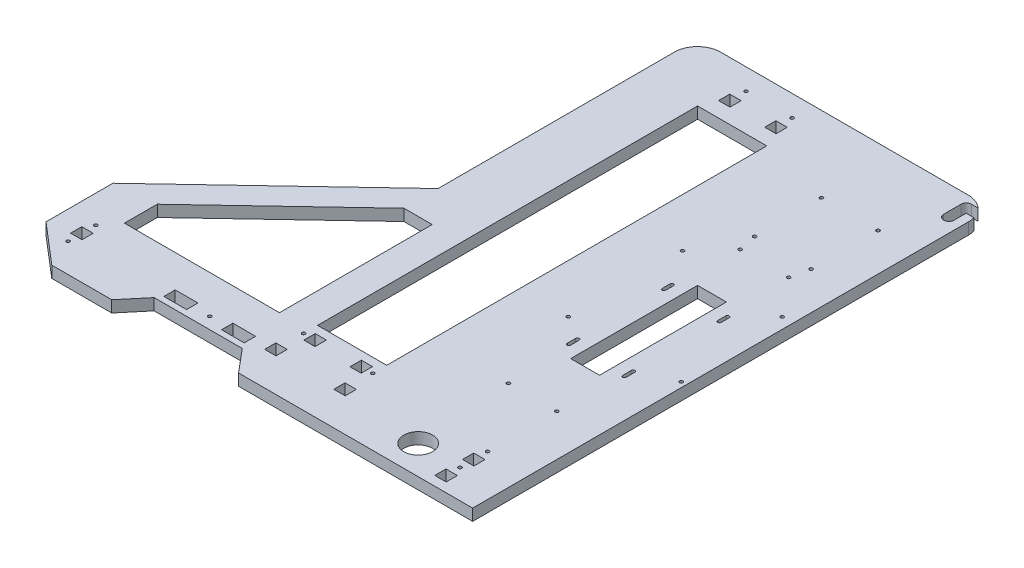
SolidWorks part; units mm, degrees
ref_plane "Front Plane" through (0, 0, 0) normal (0, 0, 1) x (1, 0, 0)
ref_plane "Top Plane" through (0, 0, 0) normal (0, 1, 0) x (1, 0, 0)
ref_plane "Right Plane" through (0, 0, 0) normal (1, 0, 0) x (0, 0, -1)
sketch "Sketch1" plane through (0, 0, 0) normal (0, 1, 0) x (1, 0, 0)
  line L0 (0, 0) -> (-235, 0)
  line L1 (-235, 0) -> (-235, -225)
  line L2 (-235, -225) -> (-380, -362)
  line L3 (-380, -362) -> (-380, -420)
  line L4 (-380, -420) -> (-345, -450)
  line L5 (-345, -450) -> (-293, -450)
  line L6 (-293, -450) -> (-263.6315, -415)
  line L7 (-263.6315, -415) -> (-212.3685, -415)
  line L8 (-212.3685, -415) -> (-183, -450)
  line L9 (-183, -450) -> (0, -450)
  line L10 (0, 0) -> (0, -450)
  line L12 (-293, -450) -> (-183, -450) construction
  dimension "D3" = 235
  dimension "D5" = 58
  dimension "D13" = 190
  dimension "D7" = 35
  dimension "D15" = 52
  dimension "D12" = 30
  dimension "D10" = 35
  dimension "D6" = 380
  dimension "D4" = 450
  dimension "D2" = 50
  dimension "D8" = 50
  dimension "D9" = 110
extrude "Boss-Extrude1" add sketch "Sketch1" along normal blind 10
sketch "Sketch16" plane through (0, 10, 0) normal (0, 1, 0) x (1, 0, 0)
  line L0 (0, -450) -> (20, -450)
  line L1 (20, -450) -> (20, 0)
  line L2 (20, 0) -> (0, 0)
  line L3 (0, 0) -> (0, -450)
  dimension "D1" = 20
  dimension "D2" = 90
extrude "Boss-Extrude2" add sketch "Sketch16" against normal through all
sketch "Sketch2" plane through (0, 10, 0) normal (0, 1, 0) x (1, 0, 0)
  line L0 (-235, -225) -> (-235, -415) construction
  line L1 (-263.6315, -415) -> (-212.3685, -415) construction
  line L2 (-345, -450) -> (-345, -328.931) construction
  line L3 (-235, -225) -> (-380, -362) construction
  line L4 (-345, -358.5097) -> (-235, -254.5787)
  line L5 (-235, -254.5787) -> (-210.5, -254.5787)
  line L6 (-210.5, -254.5787) -> (-210.5, -387)
  line L7 (-210.5, -387) -> (-345, -387)
  line L8 (-345, -387) -> (-345, -358.5097)
  line L9 (0, -450) -> (0, 0) construction
  line L10 (-184.5, -380) -> (-124.5, -380)
  line L11 (-184.5, -380) -> (-184.5, -50.425)
  line L12 (-184.5, -50.425) -> (-124.5, -50.425)
  line L13 (-124.5, -380) -> (-124.5, -50.425)
  line L14 (-124.5, -392.1) -> (-184.5, -392.1) construction
  line L15 (-16, -450) -> (-16, 0) construction
  line L16 (20, 0) -> (-235, 0) construction
  line L17 (-355.9, -440.6571) -> (-355.9, -339.2297) construction
  line L18 (-20.925, -441.85) -> (-11.075, -441.85)
  line L19 (-20.925, -441.85) -> (-20.925, -432.15)
  line L20 (-20.925, -432.15) -> (-11.075, -432.15)
  line L21 (-11.075, -441.85) -> (-11.075, -432.15)
  line L22 (-20.925, -441.85) -> (-11.075, -432.15) construction
  line L23 (-20.925, -432.15) -> (-11.075, -441.85) construction
  line L24 (-20.925, -417.85) -> (-11.075, -417.85)
  line L25 (-20.925, -417.85) -> (-20.925, -408.15)
  line L26 (-20.925, -408.15) -> (-11.075, -408.15)
  line L27 (-11.075, -417.85) -> (-11.075, -408.15)
  line L28 (-20.925, -417.85) -> (-11.075, -408.15) construction
  line L29 (-20.925, -408.15) -> (-11.075, -417.85) construction
  line L30 (-380, -420) -> (-345, -450) construction
  line L32 (-350.975, -408.15) -> (-360.825, -408.15)
  line L33 (-350.975, -408.15) -> (-350.975, -417.85)
  line L34 (-350.975, -417.85) -> (-360.825, -417.85)
  line L35 (-360.825, -408.15) -> (-360.825, -417.85)
  line L36 (-350.975, -408.15) -> (-360.825, -417.85) construction
  line L37 (-350.975, -417.85) -> (-360.825, -408.15) construction
  line L38 (-183, -450) -> (20, -450) construction
  line L39 (-183, -450) -> (20, -450) construction
  line L40 (-173.749, -32.425) -> (-113.749, -32.425) construction
  line L41 (-154.5, -50.425) -> (-154.5, -32.425) construction
  line L42 (-179.425, -27.575) -> (-169.575, -27.575)
  line L43 (-179.425, -27.575) -> (-179.425, -37.275)
  line L44 (-179.425, -37.275) -> (-169.575, -37.275)
  line L45 (-169.575, -27.575) -> (-169.575, -37.275)
  line L46 (-179.425, -27.575) -> (-169.575, -37.275) construction
  line L47 (-179.425, -37.275) -> (-169.575, -27.575) construction
  line L48 (-129.575, -37.275) -> (-139.425, -27.575) construction
  line L49 (-129.575, -27.575) -> (-139.425, -37.275) construction
  line L50 (-139.425, -27.575) -> (-139.425, -37.275)
  line L51 (-129.575, -37.275) -> (-139.425, -37.275)
  line L52 (-129.575, -27.575) -> (-129.575, -37.275)
  line L53 (-129.575, -27.575) -> (-139.425, -27.575)
  line L54 (-174.5, -32.425) -> (-174.5, -18.425) construction
  line L55 (-134.5, -32.425) -> (-134.5, -18.425) construction
  line L56 (-154.5, -380) -> (-154.5, -450) construction
  line L57 (-174.5, -392.1) -> (-134.5, -392.1) construction
  line L58 (-129.65, -397.025) -> (-139.35, -387.175) construction
  line L59 (-179.35, -387.175) -> (-169.65, -387.175)
  line L60 (-179.35, -387.175) -> (-179.35, -397.025)
  line L61 (-179.35, -397.025) -> (-169.65, -397.025)
  line L62 (-169.65, -387.175) -> (-169.65, -397.025)
  line L63 (-179.35, -387.175) -> (-169.65, -397.025) construction
  line L64 (-179.35, -397.025) -> (-169.65, -387.175) construction
  line L65 (-129.65, -387.175) -> (-139.35, -397.025) construction
  line L66 (-139.35, -387.175) -> (-139.35, -397.025)
  line L67 (-129.65, -397.025) -> (-139.35, -397.025)
  line L68 (-129.65, -387.175) -> (-129.65, -397.025)
  line L69 (-129.65, -387.175) -> (-139.35, -387.175)
  line L70 (-119.575, -420.95) -> (-129.425, -411.25) construction
  line L71 (-189.425, -411.25) -> (-179.575, -411.25)
  line L72 (-189.425, -411.25) -> (-189.425, -420.95)
  line L73 (-189.425, -420.95) -> (-179.575, -420.95)
  line L74 (-179.575, -411.25) -> (-179.575, -420.95)
  line L75 (-189.425, -411.25) -> (-179.575, -420.95) construction
  line L76 (-189.425, -420.95) -> (-179.575, -411.25) construction
  line L77 (-119.575, -411.25) -> (-129.425, -420.95) construction
  line L78 (-129.425, -411.25) -> (-129.425, -420.95)
  line L79 (-119.575, -420.95) -> (-129.425, -420.95)
  line L80 (-119.575, -411.25) -> (-119.575, -420.95)
  line L81 (-119.575, -411.25) -> (-129.425, -411.25)
  line L82 (-360.825, -408.15) -> (-11.075, -408.15) construction
  circle A0 centre (-16, -425) radius 1.45
  circle A1 centre (-16, -401) radius 1.45
  circle A2 centre (-355.9, -425) radius 1.45
  circle A3 centre (-355.9, -401) radius 1.45
  circle A4 centre (-174.5, -18.425) radius 1.45
  circle A5 centre (-134.5, -18.425) radius 1.45
  circle A6 centre (-124.5, -392.1) radius 1.45
  circle A7 centre (-184.5, -392.1) radius 1.45
  point P25 (-16, -437)
  point P30 (-16, -413)
  point P44 (-355.9, -413)
  point P61 (-174.5, -32.425)
  point P72 (-134.5, -32.425)
  point P85 (-174.5, -392.1)
  point P94 (-134.5, -392.1)
  point P95 (-184.5, -416.1)
  point P104 (-124.5, -416.1)
  point P105 (-154.5, -392.1)
  dimension "D13" = 2.9
  dimension "D14" = 2.9
  dimension "D23" = 2.9
  dimension "D24" = 2.9
  dimension "D31" = 2.9
  dimension "D37" = 2.9
  dimension "D1" = 21.5
  dimension "D2" = 28
  dimension "D3" = 24.5
  dimension "D4" = 60
  dimension "D7" = 26
  dimension "D8" = 9.7
  dimension "D9" = 9.85
  dimension "D10" = 9.85
  dimension "D11" = 9.7
  dimension "D12" = 24
  dimension "D15" = 24
  dimension "D19" = 9.85
  dimension "D20" = 9.7
  dimension "D26" = 12
  dimension "D27" = 9.85
  dimension "D28" = 9.7
  dimension "D33" = 9.7
  dimension "D38" = 9.85
  dimension "D39" = 9.7
  dimension "D41" = 24
  dimension "D34" = 30
  dimension "D36" = 12.1
  dimension "D30" = 18
  dimension "D29" = 40
  dimension "D17" = 13
  dimension "D32" = 14
  dimension "D35" = 20
  dimension "D16" = 12
  dimension "D21" = 90
  dimension "D25" = 24
  dimension "D5" = 359.75
  dimension "D22" = 349.75
  dimension "D40" = 30
  dimension "D6" = 70
  dimension "D42" = 0
  dimension "D43" = 0
  dimension "D18" = 16
  dimension "D44" = 9.85
extrude "Cut-Extrude1" cut sketch "Sketch2" against normal through all
fillet "Fillet1" radius 20 2 edges at (-235, 5, 0) (20, 5, 0)
sketch "Sketch11" plane through (0, 10, 0) normal (0, 1, 0) x (1, 0, 0)
  line L0 (-124.5, -215.2125) -> (20, -215.2125) construction
  line L1 (20, -450) -> (20, -20) construction
  line L3 (-52.25, -215.2125) -> (-52.25, -450) construction
  line L6 (-124.5, -380) -> (-124.5, -50.425) construction
  line L8 (-183, -450) -> (20, -450) construction
  circle A0 centre (-52.25, -425) radius 12.5
  circle A1 centre (-16, -425) radius 1.45 construction
  dimension "D1" = 25
  dimension "D2" = 0
  dimension "D3" = 0
extrude "WiringHole" cut sketch "Sketch11" against normal through all
sketch "Sketch9" [suppressed] plane through (0, 10, 0) normal (0, 1, 0) x (1, 0, 0)
  line L0 (-52.25, -412.5) -> (-52.25, 0) construction
  line L1 (0, 0) -> (-215, 0) construction
  line L2 (-124.5, -215.2125) -> (20, -215.2125) construction
  line L3 (-124.5, -380) -> (-124.5, -50.425) construction
  line L4 (-4.75, -126.7125) -> (-4.75, -303.7125) construction
  line L6 (-99.75, -126.7125) -> (-4.75, -126.7125) construction
  line L7 (-4.75, -303.7125) -> (-99.75, -303.7125) construction
  line L8 (-99.75, -303.7125) -> (-99.75, -126.7125) construction
  line L9 (20, -450) -> (20, -20) construction
  circle A0 centre (-52.25, -425) radius 12.5 construction
  circle A1 centre (-99.75, -126.7125) radius 1.45
  circle A2 centre (-4.75, -126.7125) radius 1.45
  circle A3 centre (-4.75, -303.7125) radius 1.45
  circle A4 centre (-99.75, -303.7125) radius 1.45
  dimension "D3" = 2.9
  dimension "D4" = 2.9
  dimension "D1" = 95
  dimension "D2" = 177
  dimension "D5" = 47.5
extrude "MountingHoles-PSU" [suppressed] cut sketch "Sketch9" against normal through all
sketch "Sketch10" plane through (0, 10, 0) normal (0, 1, 0) x (1, 0, 0)
  line L0 (-124.5, -215.2125) -> (20, -215.2125) construction
  line L1 (20, -450) -> (20, -20) construction
  line L2 (-49.75, -240.2125) -> (-24.75, -240.2125) construction
  line L3 (-37.25, -210.225) -> (-37.25, 0) construction
  line L4 (-52.25, -215.2125) -> (-52.25, -184.5972) construction
  line L7 (-124.5, -380) -> (-124.5, -50.425) construction
  line L8 (-49.75, -295.2125) -> (-24.75, -295.2125)
  line L9 (-49.75, -295.2125) -> (-49.75, -185.2125)
  line L10 (-49.75, -185.2125) -> (-24.75, -185.2125)
  line L11 (-24.75, -295.2125) -> (-24.75, -185.2125)
  line L12 (-49.75, -295.2125) -> (-24.75, -185.2125) construction
  line L13 (-49.75, -185.2125) -> (-24.75, -295.2125) construction
  line L15 (0, 0) -> (-215, 0) construction
  line L17 (-37.25, -210.225) -> (-37.25, -450) construction
  line L18 (-183, -450) -> (20, -450) construction
  line L19 (-64.75, -215.2125) -> (-39.75, -215.2125) construction
  line L20 (-37.25, -295.2125) -> (-37.25, -185.2125) construction
  dimension "D1" = 25
  dimension "D2" = 110
  dimension "D3" = 0
  dimension "D4" = 0
  dimension "D5" = 0
  dimension "D6" = 25
  dimension "D7" = 15
extrude "WiringSlot" cut sketch "Sketch10" against normal through all
sketch "CenterLines" plane through (0, 10, 0) normal (0, 1, 0) x (1, 0, 0)
  line L0 (-37.25, -295.2125) -> (-37.25, -185.2125) construction
  line L1 (-49.75, -295.2125) -> (-24.75, -295.2125) construction
  line L2 (-24.75, -185.2125) -> (-49.75, -185.2125) construction
  line L3 (-49.75, -240.2125) -> (-24.75, -240.2125) construction
  line L4 (-49.75, -185.2125) -> (-49.75, -295.2125) construction
  line L5 (-24.75, -295.2125) -> (-24.75, -185.2125) construction
ref_plane "Plane1" through (-37.25, 0, 0) normal (1, 0, 0) x (0, 0, -1)
sketch "Sketch6" plane through (0, 10, 0) normal (0, 1, 0) x (1, 0, 0)
  line L0 (-37.25, -295.2125) -> (-37.25, -185.2125) construction
  line L1 (-61.35, -240.2125) -> (-13.15, -240.2125) construction
  line L2 (-13.15, -195.7625) -> (-13.15, -278.2625) construction
  line L3 (-49.75, -295.2125) -> (-24.75, -295.2125) construction
  line L4 (-49.75, -240.2125) -> (-24.75, -240.2125) construction
  line L5 (-24.75, -185.2125) -> (-49.75, -185.2125) construction
  line L6 (-13.15, -195.7625) -> (-13.15, -202.7625) construction
  line L7 (-11.7, -195.7625) -> (-11.7, -202.7625)
  line L8 (-14.6, -195.7625) -> (-14.6, -202.7625)
  line L9 (-49.75, -240.2125) -> (-24.75, -240.2125) construction
  line L10 (-49.75, -185.2125) -> (-49.75, -295.2125) construction
  line L11 (-24.75, -295.2125) -> (-24.75, -185.2125) construction
  line L12 (-13.15, -285.2625) -> (-13.15, -278.2625) construction
  line L13 (-14.6, -285.2625) -> (-14.6, -278.2625)
  line L14 (-61.35, -277.6625) -> (-61.35, -202.7625) construction
  line L15 (-13.15, -285.2625) -> (-13.15, -202.7625) construction
  line L16 (-11.7, -285.2625) -> (-11.7, -278.2625)
  arc A2 (-11.7, -195.7625) -> (-14.6, -195.7625) centre (-13.15, -195.7625) ccw
  arc A3 (-14.6, -202.7625) -> (-11.7, -202.7625) centre (-13.15, -202.7625) ccw
  circle A4 centre (-61.35, -277.6625) radius 1.45
  circle A6 centre (-61.35, -202.7625) radius 1.45
  arc A8 (-14.6, -285.2625) -> (-11.7, -285.2625) centre (-13.15, -285.2625) ccw
  arc A9 (-11.7, -278.2625) -> (-14.6, -278.2625) centre (-13.15, -278.2625) ccw
  point P20 (-13.15, -199.2625)
  point P25 (-13.15, -281.7625)
  dimension "D6" = 0
  dimension "D8" = 2.9
  dimension "D12" = 2.9
  dimension "D4" = 1.45
  dimension "D5" = 1.45
  dimension "D11" = 82.5
  dimension "D14" = 74.9
  dimension "D2" = 24.1
  dimension "D3" = 48.2
  dimension "D9" = 7
  dimension "D10" = 7
extrude "MountingHoles-RAMPS" cut sketch "Sketch6" against normal through all
mirror "Mirror1" about plane through (-37.25, 0, 0) normal (1, 0, 0) of "MountingHoles-RAMPS"
sketch "Sketch5" plane through (0, 10, 0) normal (0, 1, 0) x (1, 0, 0)
  line L0 (-24.75, -240.2125) -> (-49.75, -240.2125) construction
  line L3 (-24.75, -295.2125) -> (-24.75, -185.2125) construction
  line L5 (-49.75, -185.2125) -> (-49.75, -295.2125) construction
  line L7 (-16.25, -139.7125) -> (-58.25, -139.7125) construction
  line L8 (-16.25, -340.7125) -> (-58.25, -340.7125) construction
  line L9 (-37.25, -240.2125) -> (-37.25, -139.7125) construction
  line L10 (-37.25, -240.2125) -> (-37.25, -340.7125) construction
  circle A0 centre (-58.25, -139.7125) radius 1.45
  circle A1 centre (-16.25, -139.7125) radius 1.45
  circle A2 centre (-16.25, -340.7125) radius 1.45
  circle A3 centre (-58.25, -340.7125) radius 1.45
  point P17 (-37.25, -139.7125)
  point P22 (-37.25, -340.7125)
  dimension "D2" = 2.9
  dimension "D5" = 2.9
  dimension "D6" = 2.9
  dimension "D7" = 2.9
  dimension "D3" = 201
  dimension "D4" = 100.5
  dimension "D8" = 21
  dimension "D9" = 21
  dimension "D10" = 100.5
extrude "MountingHoles-Melzi" cut sketch "Sketch5" against normal through all
sketch "Sketch13" plane through (0, 0, 0) normal (0, -1, 0) x (-1, 0, 0)
  line L0 (49.75, -215.2125) -> (124.5, -215.2125) construction
  line L1 (124.5, -380) -> (124.5, -50.425) construction
  line L2 (82.25, -264.7275) -> (82.25, -165.6975) construction
  line L3 (37.25, -295.2125) -> (37.25, -185.2125) construction
  line L4 (49.75, -185.2125) -> (49.75, -295.2125) construction
  line L6 (82.25, -264.7275) -> (-15.65, -264.7275) construction
  circle A0 centre (82.25, -165.6975) radius 1.45
  circle A1 centre (82.25, -264.7275) radius 1.45
  circle A2 centre (-10.59, -172.1775) radius 1.45
  circle A3 centre (-15.65, -264.7275) radius 1.45
  point P11 (82.25, -215.2125)
  dimension "D8" = 2.9
  dimension "D6" = 2.9
  dimension "D1" = 2.9
  dimension "D2" = 49.515
  dimension "D3" = 45
  dimension "D4" = 6.48
  dimension "D5" = 92.84
  dimension "D7" = 97.9
extrude "Mountingholes-Smoothieboard" cut sketch "Sketch13" against normal through all
mirror "Flipped" [suppressed] about plane through (-37.25, 0, 0) normal (1, 0, 0)
sketch "Sketch21" plane through (0, 10, 0) normal (0, 1, 0) x (1, 0, 0)
  line L0 (-37.25, -185.2125) -> (-37.25, 0) construction
  line L1 (-24.75, -185.2125) -> (-49.75, -185.2125) construction
  line L2 (0, 0) -> (-215, 0) construction
  line L3 (-37.25, -94.7125) -> (-23.3697, -94.7125) construction
  circle A0 centre (-12.75, -65.7125) radius 1.45
  circle A1 centre (-61.75, -65.7125) radius 1.45
  circle A2 centre (-61.75, -123.7125) radius 1.45
  circle A3 centre (-12.75, -123.7125) radius 1.45
  circle A4 centre (-16.25, -139.7125) radius 1.45 construction
  dimension "D1" = 2.9
  dimension "D2" = 24.5
  dimension "D3" = 29
  dimension "D4" = 45
extrude "Pi" cut sketch "Sketch21" against normal through all
sketch "Sketch17" plane through (0, 10, 0) normal (0, 1, 0) x (1, 0, 0)
  line L0 (0, 0) -> (20, 0) construction
  line L1 (20, -23.6361) -> (20, 0) construction
  line L2 (20, -450) -> (20, -20) construction
  line L3 (20, -10) -> (8, -10) construction
  line L4 (20, -14.5) -> (8, -14.5)
  line L5 (20, -5.5) -> (8, -5.5)
  arc A0 (20, -14.5) -> (20, -5.5) centre (20, -10) ccw
  arc A1 (8, -5.5) -> (8, -14.5) centre (8, -10) ccw
  point P8 (14, -10)
  dimension "D1" = 9
  dimension "D2" = 12
  dimension "D3" = 10
extrude "Cut-Extrude3" cut sketch "Sketch17" against normal through all
sketch "Sketch18" plane through (0, 10, 0) normal (0, 1, 0) x (1, 0, 0)
  line L0 (8, -5.5) -> (8, -14.5) construction
  line L1 (3.5, -10) -> (8, -10) construction
  line L2 (8, -10) -> (8, -25) construction
  line L3 (12.5, -10) -> (12.5, -25)
  line L4 (3.5, -10) -> (3.5, -25)
  arc A0 (8, -5.5) -> (8, -14.5) centre (8, -10) ccw construction
  arc A1 (12.5, -10) -> (3.5, -10) centre (8, -10) ccw
  arc A2 (3.5, -25) -> (12.5, -25) centre (8, -25) ccw
  point P10 (8, -17.5)
  dimension "D1" = 9
  dimension "D2" = 0
  dimension "D3" = 15
extrude "Cut-Extrude4" cut sketch "Sketch18" against normal through all
sketch "Sketch19" plane through (0, 10, 0) normal (0, 1, 0) x (1, 0, 0)
  line L0 (-2, -25) -> (18, -25) construction
  line L1 (8, -25) -> (8, -5.5) construction
  circle A0 centre (18, -25) radius 1.45
  arc A1 (8, -5.5) -> (3.5, -10) centre (8, -10) ccw construction
  circle A2 centre (-2, -25) radius 1.45
  dimension "D2" = 2.9
extrude "Cut-Extrude5" [suppressed] cut sketch "Sketch19" against normal through all
sketch "Sketch22" plane through (0, 10, 0) normal (0, 1, 0) x (1, 0, 0)
  line L0 (-276.218, -430) -> (-199.782, -430)
  line L1 (-293, -450) -> (-263.6315, -415) construction
  line L2 (-212.3685, -415) -> (-183, -450) construction
  line L3 (-199.782, -430) -> (-212.3685, -415)
  line L4 (-212.3685, -415) -> (-263.6315, -415)
  line L5 (-263.6315, -415) -> (-276.218, -430)
  dimension "D1" = 15
extrude "Boss-Extrude3" add sketch "Sketch22" against normal through all
sketch "Sketch23" plane through (0, 10, 0) normal (0, 1, 0) x (1, 0, 0)
  line L0 (-238, -430) -> (-238, -387) construction
  line L1 (-276.218, -430) -> (-199.782, -430) construction
  line L2 (-345, -387) -> (-210.5, -387) construction
  line L3 (-213, -420) -> (-263, -420) construction
  line L4 (-179.35, -387.175) -> (-179.35, -397.025) construction
  line L5 (-272.85, -415.075) -> (-253.15, -415.075)
  line L6 (-272.85, -415.075) -> (-272.85, -424.925)
  line L7 (-272.85, -424.925) -> (-253.15, -424.925)
  line L8 (-253.15, -415.075) -> (-253.15, -424.925)
  line L9 (-272.85, -415.075) -> (-253.15, -424.925) construction
  line L10 (-272.85, -424.925) -> (-253.15, -415.075) construction
  line L11 (-203.15, -424.925) -> (-222.85, -415.075) construction
  line L12 (-203.15, -415.075) -> (-222.85, -424.925) construction
  line L13 (-222.85, -415.075) -> (-222.85, -424.925)
  line L14 (-203.15, -424.925) -> (-222.85, -424.925)
  line L15 (-203.15, -415.075) -> (-203.15, -424.925)
  line L16 (-203.15, -415.075) -> (-222.85, -415.075)
  circle A0 centre (-238, -420) radius 1.45
  point P19 (-238, -420)
  dimension "D4" = 2.9
  dimension "D1" = 19.7
  dimension "D3" = 10
extrude "Cut-Extrude6" cut sketch "Sketch23" against normal through all
equation "\"Y-ROD-SPACING\"=75"
equation "\"Y-BED-OFFSET\"=2"
equation "\"Y-BED-ROD-INSET\"=3.5"
equation "\"T-SLOT-NUT-FILLET-RADIUS\"=0.5"
equation "\"T-SLOT-SCREW-SHAFT-RADIUS\"=1.55"
equation "\"T-SLOT-SCREW-SHAFT-CUTOUT-LENGTH\"=11"
equation "\"T-SLOT-NUT-DEPTH\"=3.5"
equation "\"T-SLOT-NUT-WIDTH\"=2.85"
equation "\"T-SLOT-NUT-END-DISTANCE\"=8"
equation "\"ACRYLIC-TAB-CUTOUT-SIZE\"=\"ACRYLIC-THICKNESS\"+\"ACRYLIC-TAB-TOLERANCE\"*2"
equation "\"ACRYLIC-TAB-WIDTH\"=\"ACRYLIC-THICKNESS\""
equation "\"ACRYLIC-M3-HOLE\"=2.9"
equation "\"SMOOTHROD-CAP-SCREW-DISTANCE\"=20"
equation "\"FRAME-WIDTH-INNER\"=370"
equation "\"D24@Sketch2\"=\"ACRYLIC-M3-HOLE\""
equation "\"D23@Sketch2\"=\"ACRYLIC-M3-HOLE\""
equation "\"D19@Sketch2\"=\"ACRYLIC-THICKNESS\"-\"KERF\"*2"
equation "\"D20@Sketch2\"=\"ACRYLIC-TAB-WIDTH\"-\"KERF\"*4"
equation "\"D37@Sketch2\"=\"ACRYLIC-M3-HOLE\""
equation "\"D33@Sketch2\"=\"ACRYLIC-TAB-WIDTH\"-\"KERF\"*4"
equation "\"D38@Sketch2\"=\"ACRYLIC-THICKNESS\"-\"KERF\"*2"
equation "\"D39@Sketch2\"=\"ACRYLIC-TAB-WIDTH\"-\"KERF\"*4"
equation "\"D13@Sketch2\"=\"ACRYLIC-M3-HOLE\""
equation "\"D14@Sketch2\"=\"ACRYLIC-M3-HOLE\""
equation "\"D8@Sketch2\"=\"ACRYLIC-TAB-WIDTH\"-\"KERF\"*4"
equation "\"D9@Sketch2\"=\"ACRYLIC-THICKNESS\"-\"KERF\"*2"
equation "\"D10@Sketch2\"=\"ACRYLIC-THICKNESS\"-\"KERF\"*2"
equation "\"D11@Sketch2\"=\"ACRYLIC-TAB-WIDTH\"-\"KERF\"*4"
equation "\"D31@Sketch2\"=\"ACRYLIC-M3-HOLE\""
equation "\"D27@Sketch2\"=\"ACRYLIC-THICKNESS\"-\"KERF\"*2"
equation "\"D28@Sketch2\"=\"ACRYLIC-TAB-WIDTH\"-\"KERF\"*4"
equation "\"NEMA17-HOLE-SPACING\"=31"
equation "\"NEMA17-CENTRAL-CUTOUT\"=22.5"
equation "\"Z-BRACKET-REACH\"=57"
equation "\"TOP-BRACKET-SPACING\"=40"
equation "\"D29@Sketch2\"=\"TOP-BRACKET-SPACING\""
equation "\"ACRYLIC-THICKNESS\"=10"
equation "\"SMOOTHROD-Z-LENGTH\"=350"
equation "\"D5@Sketch2\"=\"SMOOTHROD-Z-LENGTH\"-\"SMOOTHROD-TIGHTENING-HEADROOM\"+10"
equation "\"SMOOTHROD-X-LENGTH\"=350"
equation "\"SMOOTHROD-Y-LENGTH\"=350"
equation "\"D22@Sketch2\"=\"SMOOTHROD-Y-LENGTH\"-\"SMOOTHROD-TIGHTENING-HEADROOM\""
equation "\"SMOOTHROD-TIGHTENING-HEADROOM\"=.25"
equation "\"X-ROD-SPACING\"=45"
equation "\"Z-ROD-SPACING\"=17.5"
equation "\"LEADSCREW-Z-LENGTH\"=300"
equation "\"SCREW-HEAD-RADIUS\"=6"
equation "\"PRINTED-X-SMOOTHROD-DIAMETER\"=8.8"
equation "\"PRINTED-X-SMOOTHROD-CUTOUT\"=10"
equation "\"PRINTED-X-BASE-HEIGHT\"=10"
equation "\"PRINTED-LM8UU-CUTOUT-SIZE\"=15.5"
equation "\"PRINTED-LM8UU-CUTOUT-LENGTH\"=24.5"
equation "\"PRINTED-X-IDLER-HEIGHT\"=16"
equation "\"PSU-MOUNTING-WIDTH\"=95"
equation "\"PSU-MOUNTING-HEIGHT\"=177"
equation "\"D1@Sketch9\"=\"PSU-MOUNTING-WIDTH\""
equation "\"D3@Sketch9\"=\"ACRYLIC-M3-HOLE\""
equation "\"D1@Boss-Extrude1\"=\"ACRYLIC-THICKNESS\""
equation "\"D6@Sketch1\"=\"SMOOTHROD-Y-LENGTH\"+30"
equation "\"D4@Sketch9\"=\"ACRYLIC-M3-HOLE\""
equation "\"D2@Sketch9\"=\"PSU-MOUNTING-HEIGHT\""
equation "\"D5@Sketch9\"=\"PSU-MOUNTING-WIDTH\"/2"
equation "\"D4@Sketch1\"=\"SMOOTHROD-Z-LENGTH\"+100"
equation "\"D8@Sketch6\"=\"ACRYLIC-M3-HOLE\""
equation "\"D12@Sketch6\"=\"ACRYLIC-M3-HOLE\""
equation "\"D2@Sketch5\"=\"ACRYLIC-M3-HOLE\""
equation "\"D5@Sketch5\"=\"ACRYLIC-M3-HOLE\""
equation "\"D6@Sketch5\"=\"ACRYLIC-M3-HOLE\""
equation "\"D7@Sketch5\"=\"ACRYLIC-M3-HOLE\""
equation "\"D1@Sketch13\"=\"ACRYLIC-M3-HOLE\""
equation "\"D6@Sketch13\"=\"ACRYLIC-M3-HOLE\""
equation "\"D8@Sketch13\"=\"ACRYLIC-M3-HOLE\""
equation "\"D4@Sketch6\"=\"ACRYLIC-M3-HOLE\"/2"
equation "\"D5@Sketch6\"=\"ACRYLIC-M3-HOLE\"/2"
equation "\"Y-BED-SCREW-SPACING\"=209"
equation "\"Y-BED-SCREW-CUTOUT-SLOT-HEIGHT\"=2.5"
equation "\"ACRYLIC-THICKNESS2\"=4.5"
equation "\"ACRYLIC-TAB-TOLERANCE\"=-.05"
equation "\"Z-ROD-INSET\"=13.5"
equation "\"SCREW-LENGTH-FRAME\"=\"ACRYLIC-THICKNESS\" + 10"
equation "\"SCREW-LENGTH-MOTOR\"=\"ACRYLIC-THICKNESS\" + 5"
equation "\"SCREW-LENGTH-EXTRUDER\"=28"
equation "\"Y-BELT-TO-ROD-DISTANCE\"=20"
equation "\"SPOOL-HOLDER-ROD-SPACING\"=150"
equation "\"ACRYLIC-X-CARRIAGE-WIDTH\"=55"
equation "\"ACRYLIC-X-CARRIAGE-HEIGHT\"=75"
equation "\"ACRYLIC-X-CARRIAGE-LM8UU-CUTOUT-WIDTH\"=24.25"
equation "\"ACRYLIC-X-CARRIAGE-SCREW-SPACING-X\"=15"
equation "\"ACRYLIC-X-CARRIAGE-SCREW-SPACING-Y\"=33"
equation "\"ACRYLIC-X-CARRIAGE-CENTER-TAB-SPACING\"=14"
equation "\"ACRYLIC-X-CARRIAGE-EXTRUDER-OFFSET\"=26"
equation "\"ACRYLIC-X-CARRIAGE-EXTRUDER-ANGLE\"=90"
equation "\"ACRYLIC-X-CARRIAGE-EXTRUDER-SHELF-DEPTH\"=\"ACRYLIC-X-CARRIAGE-EXTRUDER-OFFSET\" + 28"
equation "\"ACRYLIC-X-CARRIAGE-EXTRUDER-BRACE-SPACING\"=23"
equation "\"ACRYLIC-X-CARRIAGE-EXTRUDER-BRACE-TAB-OFFSET\"=20"
equation "\"ACRYLIC-X-CARRIAGE-EXTRUDER-BRACE-HEIGHT\"=35"
equation "\"ACRYLIC-X-CARRIAGE-EXTRUDER-BRACE-SCREW-SPACING\"=22"
equation "\"D1@Sketch19\"=\"SMOOTHROD-CAP-SCREW-DISTANCE\"/2"
equation "\"D2@Sketch19\"=\"ACRYLIC-M3-HOLE\""
equation "\"D1@Sketch21\"=\"ACRYLIC-M3-HOLE\""
equation "\"KERF\"=0.075"
equation "\"PRINTED-M3-HOLE\"=3.5"
equation "\"PRINTED-M3-NUT-AF\"=6.25"
equation "\"ACRYLIC-X-CARRIAGE-LM8UU-CUTOUT-HEIGHT\"=11.0"
equation "\"ACRYLIC-X-CARRIAGE-DUAL-WIDTH-MULTIPLIER\"=1.65"
equation "\"ACRYLIC-X-CARRIAGE-DUAL-HOTEND-SPACING\"=42"
equation "\"ACRYLIC-X-CARRIAGE-DUAL-WIDTH\"=75"
equation "\"ACRYLIC-X-CARRIAGE-DUAL-FAN-OFFSET\"=52"
equation "\"ACRYLIC-X-CARRIAGE-DUAL-FAN-HEIGHT\"=20"
equation "\"ACRYLIC-X-CARRIAGE-DUAL-HOTEND-SEPARATION\"=36"
equation "\"ACRYLIC-X-CARRIAGE-DUAL-MOUNT-PLATE-DEPTH\"=75"
equation "\"ACRYLIC-X-CARRIAGE-DUAL-MOUNT-BRACE-WIDTH\"=33"
equation "\"ACRYLIC-X-CARRIAGE-DUAL-MOUNT-SCREW-WIDTH\"=40"
equation "\"BLOWER-FAN-WIDTH\"=15"
equation "\"D44@Sketch2\"=\"ACRYLIC-THICKNESS\"-\"KERF\"*2"
equation "\"D1@Sketch23\"=20-\"KERF\"*4"
equation "\"D4@Sketch23\"=\"ACRYLIC-M3-HOLE\""
